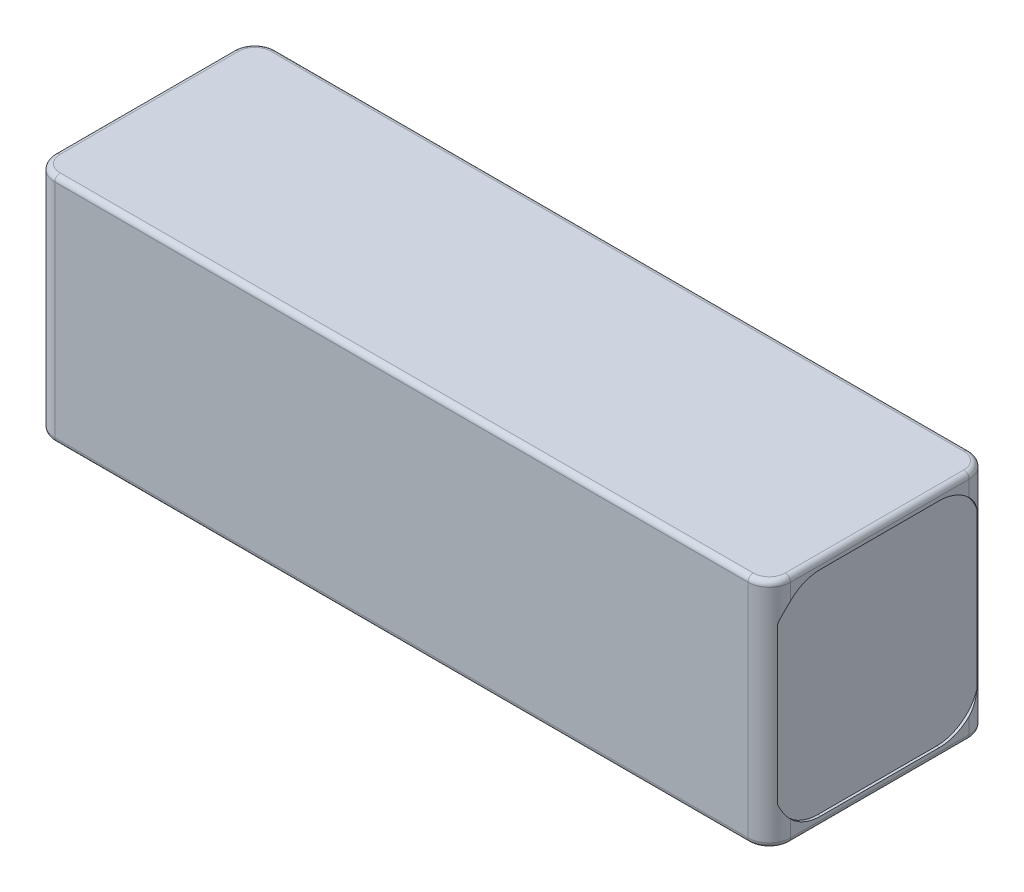
SolidWorks part; units mm, degrees
ref_plane "Front Plane" through (0, 0, 0) normal (0, 0, 1) x (1, 0, 0)
ref_plane "Top Plane" through (0, 0, 0) normal (0, 1, 0) x (1, 0, 0)
ref_plane "Right Plane" through (0, 0, 0) normal (1, 0, 0) x (0, 0, -1)
ref_plane "Plane1" through (0, 0, -15) normal (0, 0, -1) x (-1, 0, 0)
sketch "Sketch1" plane through (0, 0, -15) normal (0, 0, -1) x (-1, 0, 0)
  line L0 (-69, -22) -> (69, -22)
  line L1 (69, -22) -> (69, 21.5)
  line L2 (69, 21.5) -> (-69, 21.5)
  line L3 (-69, 21.5) -> (-69, -22)
  line L4 (-69, -0.25) -> (69, -0.25) construction
  line L5 (0, 21.5) -> (0, -22) construction
  dimension "D1" = 43.5
  dimension "D2" = 138
extrude "Boss-Extrude1" add sketch "Sketch1" against normal blind 41.5
sketch "Sketch2" plane through (69, 0, 0) normal (1, 0, 0) x (0, 0, -1)
  line L0 (-24.875, 11.7967) -> (-24.875, -12.2967)
  line L1 (-16.875, -20.2967) -> (5.375, -20.2967)
  line L2 (13.375, -12.2967) -> (13.375, 11.7967)
  line L3 (5.375, 19.7967) -> (-16.875, 19.7967)
  line L4 (-26.5, 21.5) -> (15, -22) construction
  line L5 (15, 21.5) -> (-26.5, -22) construction
  line L6 (-24.875, 19.7967) -> (13.375, -20.2967) construction
  line L7 (13.375, 19.7967) -> (-24.875, -20.2967) construction
  line L12 (-26.5, 21.5) -> (15, 21.5) construction
  line L13 (-26.5, 21.5) -> (-26.5, -22) construction
  line L14 (-26.5, -22) -> (15, -22) construction
  line L15 (15, 21.5) -> (15, -22) construction
  line L16 (-26.5, 21.5) -> (15, -22) construction
  line L17 (-26.5, -22) -> (15, 21.5) construction
  arc A0 (-24.875, -12.2967) -> (-16.875, -20.2967) centre (-16.875, -12.2967) ccw
  arc A1 (5.375, -20.2967) -> (13.375, -12.2967) centre (5.375, -12.2967) ccw
  arc A2 (13.375, 11.7967) -> (5.375, 19.7967) centre (5.375, 11.7967) ccw
  arc A3 (-24.875, 11.7967) -> (-16.875, 19.7967) centre (-16.875, 11.7967) cw
  point P16 (-5.75, -0.25)
  dimension "D3" = 8
  dimension "D1" = 38.25
  dimension "D2" = 41.5
extrude "Cut-Extrude1" cut sketch "Sketch2" against normal blind 0.5
sketch "Sketch3" plane through (-69, 0, 0) normal (-1, 0, 0) x (0, 0, 1)
  line L0 (16.875, 19.7967) -> (-5.375, 19.7967)
  line L1 (-13.375, 11.7967) -> (-13.375, -12.2967)
  line L2 (-5.375, -20.2967) -> (16.875, -20.2967)
  line L3 (24.875, -12.2967) -> (24.875, 11.7967)
  line L4 (-13.375, 19.7967) -> (24.875, -20.2967) construction
  line L5 (24.875, 19.7967) -> (-13.375, -20.2967) construction
  line L6 (-15, 21.5) -> (26.5, -22) construction
  line L7 (26.5, -22) -> (-15, -22) construction
  line L8 (-15, -22) -> (26.5, 21.5) construction
  arc A0 (-13.375, -12.2967) -> (-5.375, -20.2967) centre (-5.375, -12.2967) ccw
  arc A1 (16.875, -20.2967) -> (24.875, -12.2967) centre (16.875, -12.2967) ccw
  arc A2 (16.875, 19.7967) -> (24.875, 11.7967) centre (16.875, 11.7967) cw
  arc A3 (-5.375, 19.7967) -> (-13.375, 11.7967) centre (-5.375, 11.7967) ccw
  dimension "D3" = 8
  dimension "D1" = 38.25
  dimension "D2" = 41.5
extrude "Cut-Extrude2" cut sketch "Sketch3" against normal blind 0.5
fillet "Fillet1" radius 4 4 edges at (-69, -0.25, -15) (-69, -0.25, 26.5) (69, -0.25, -15) (69, -0.25, 26.5) tangent propagation no
fillet "Fillet2" radius 1 16 edges at (67.8284, 21.5, -13.8284) (69, 21.5, 5.75) (0, 21.5, -15) (67.8284, 21.5, 25.3284) (-67.8284, 21.5, -13.8284) (0, 21.5, 26.5) (-69, 21.5, 5.75) (-67.8284, 21.5, 25.3284) (-69, -22, 5.75) (-67.8284, -22, -13.8284) (-67.8284, -22, 25.3284) (0, -22, -15) (0, -22, 26.5) (67.8284, -22, -13.8284) (67.8284, -22, 25.3284) (69, -22, 5.75) tangent propagation no
sketch "Sketch4" plane through (0, 0, 26.5) normal (0, 0, 1) x (1, 0, 0)
  line L0 (-65, -0.25) -> (65, -0.25) construction
  line L1 (-65, 20.5) -> (-65, -21) construction
  line L2 (65, -21) -> (65, 20.5) construction
  line L3 (0, 25.9735) -> (0, -21) construction
  line L4 (-65, -21) -> (65, -21) construction
  circle A0 centre (0, -0.25) radius 0.5026
equation "\"D1@Sketch3\"=\"D2@Sketch3\" * .75"
equation "\"D1@Sketch2\"=\"D2@Sketch2\"* .75"
